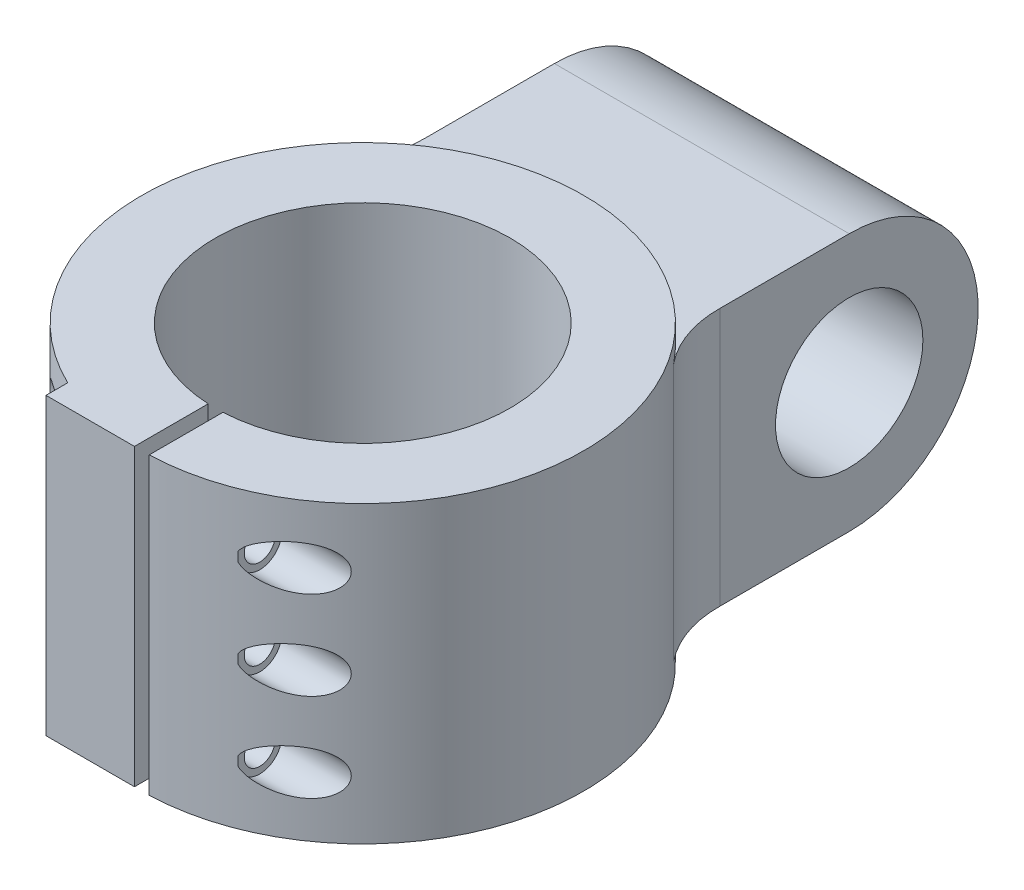
SolidWorks part; units mm, degrees
ref_plane "Płaszczyzna przednia" through (0, 0, 0) normal (0, 0, 1) x (1, 0, 0)
ref_plane "Płaszczyzna górna" through (0, 0, 0) normal (0, 1, 0) x (1, 0, 0)
ref_plane "Płaszczyzna prawa" through (0, 0, 0) normal (1, 0, 0) x (0, 0, -1)
sketch "Sketch1" plane through (0, 0, 0) normal (0, 1, 0) x (1, 0, 0)
  circle A0 centre (0, 0) radius 20
  circle A1 centre (0, 0) radius 30
  dimension "D1" = 40
  dimension "D2" = 60
extrude "Boss-Extrude1" add sketch "Sketch1" along normal blind 40
sketch "Sketch2" plane through (0, 40, 0) normal (0, 1, 0) x (1, 0, 0)
  line L0 (-1, 0) -> (1, 0)
  line L1 (1, 0) -> (1, -30)
  line L2 (1, -30) -> (-1, -30)
  line L3 (-1, -30) -> (-1, 0)
  circle A0 centre (0, 0) radius 30 construction
  point P4 (0, 0)
  dimension "D1" = 2
extrude "Cut-Extrude1" cut sketch "Sketch2" against normal through all
sketch "Sketch3" plane through (0, 40, 0) normal (0, 1, 0) x (1, 0, 0)
  line L0 (-1, -29.9833) -> (-13, -29.9833)
  line L1 (-13, -29.9833) -> (-13, -27.037)
  arc A0 (1, -29.9833) -> (-1, -29.9833) centre (0, 0) ccw construction
  arc A1 (-13, -27.037) -> (-1, -29.9833) centre (0, 0) ccw
  dimension "D1" = 12
extrude "Boss-Extrude2" add sketch "Sketch3" against normal up to surface (40 mm away) up to face at (0, 0, -0.0104)
hole_wizard "CBORE for M4 Hex Socket Head Cap Screw1" positions "Sketch4" profile "Sketch5" counterbore size "M4" standard "DIN"
sketch "Sketch4" plane through (-13, 0, 0) normal (-1, 0, 0) x (0, 0, 1)
  line L8 (29.9833, 40) -> (19.975, 40)
  line L9 (19.975, 40) -> (19.975, 0)
  line L10 (19.975, 0) -> (29.9833, 0)
  line L11 (29.9833, 0) -> (29.9833, 40)
  line L12 (29.9833, 40) -> (19.975, 40)
  line L13 (19.975, 40) -> (19.975, 0)
  line L14 (19.975, 0) -> (29.9833, 0)
  line L15 (29.9833, 0) -> (29.9833, 40)
  line L16 (19.975, 20) -> (24.9792, 20) construction
  line L18 (24.9792, 40) -> (24.9792, 20) construction
  point P0 (24.9792, 32)
  point P2 (24.9792, 20)
  point P4 (24.9792, 8)
  dimension "D2" = 12
  dimension "D3" = 12
  dimension "D1" = 0
sketch "Sketch5" plane through (-13, 32, 24.9792) normal (0, 1, 0) x (0, 0, 1)
  line L0 (0, 0) -> (0, 13.3519)
  line L1 (0, 13.3519) -> (2.25, 12)
  line L2 (2.25, 12) -> (2.25, 4)
  line L3 (2.25, 4) -> (3.75, 4)
  line L4 (3.75, 4) -> (3.75, 0)
  line L5 (3.75, 0) -> (0, 0)
  line L10 (0, 13.3519) -> (-2.25, 12) construction
  line L11 (0, -6.35) -> (0, 107.95) construction
  dimension "Hole Dia." = 4.5
  dimension "Hole Depth" = 12
  dimension "C'Bore Dia." = 7.5
  dimension "C'Bore Depth" = 4
  dimension "Drill Angle" = 118
sketch "Sketch6" plane through (-13, 0, 0) normal (-1, 0, 0) x (0, 0, 1)
  circle A0 centre (24.9792, 32) radius 3.75 construction
  circle A1 centre (24.9792, 20) radius 3.75 construction
  circle A2 centre (24.9792, 8) radius 3.75 construction
  circle A3 centre (24.9792, 32) radius 3.75
  circle A4 centre (24.9792, 20) radius 3.75
  circle A5 centre (24.9792, 8) radius 3.75
extrude "Cut-Extrude2" cut sketch "Sketch6" along normal through all
hole_wizard "Ø5.4 (5.4) Diameter Hole1" positions "Sketch7" profile "Sketch9" hole size "Ø5.4" standard "DIN" end condition through all
sketch "Sketch7" plane through (1, 0, 0) normal (-1, 0, 0) x (0, 0, 1)
  point P0 (24.9792, 8)
  point P3 (24.9792, 20)
  point P6 (24.9792, 32)
sketch "Sketch9" plane through (1, 8, 24.9792) normal (0, 1, 0) x (0, 0, 1)
  line L0 (0, 0) -> (0, 29)
  line L1 (0, 29) -> (2.1, 29)
  line L2 (2.1, 29) -> (2.1, 0)
  line L5 (2.1, 0) -> (0, 0)
  line L11 (0, -6.35) -> (0, 107.95) construction
  dimension "Thru Hole Dia." = 4.2
  dimension "Thru Hole Depth" = 29
ref_plane "Plane1" through (22, 0, 0) normal (-1, 0, 0) x (0, 0, 1)
sketch "Sketch10" plane through (22, 0, 0) normal (-1, 0, 0) x (0, 0, 1)
  circle A0 centre (24.9792, 8) radius 3
  circle A1 centre (24.9792, 32) radius 3
  circle A2 centre (24.9792, 20) radius 3
  dimension "D1" = 6
extrude "Cut-Extrude3" cut sketch "Sketch10" along normal blind 11
sketch "Sketch12" plane through (0, 40, 0) normal (0, 1, 0) x (1, 0, 0)
  line L0 (1, -29.9833) -> (1, 19.975)
  line L1 (-1, -29.9833) -> (-1, 19.975)
  line L4 (1, -19.975) -> (1, -29.9833)
  line L5 (-13, -27.037) -> (-13, -29.9833)
  line L6 (-13, -29.9833) -> (-1, -29.9833)
  line L7 (-1, -29.9833) -> (-1, -19.975)
  line L9 (-13, -27.037) -> (-13, -29.9833)
  line L10 (-13, -29.9833) -> (-1, -29.9833)
  arc A0 (1, -19.975) -> (-1, -19.975) centre (0, 0) ccw construction
  arc A2 (1, -29.9833) -> (-13, -27.037) centre (0, 0) ccw
  arc A3 (1, -19.975) -> (-1, -19.975) centre (0, 0) ccw
  arc A4 (1, -29.9833) -> (-13, -27.037) centre (0, 0) ccw
  arc A7 (1, 19.975) -> (-1, 19.975) centre (0, 0) ccw
  dimension "D1" = 0
extrude "Boss-Extrude3" [suppressed] add sketch "Sketch12" along normal blind 4
sketch "Sketch13" plane through (0, 0, 0) normal (1, 0, 0) x (0, 0, -1)
  line L0 (30, 40) -> (30, 0) construction
  line L1 (30, 20) -> (36, 20) construction
  line L2 (36, 20) -> (46, 20) construction
  line L3 (46, 37.5) -> (30, 37.5)
  line L4 (46, 2.5) -> (30, 2.5)
  line L5 (30, 2.5) -> (28.5, 2.5)
  line L6 (28.5, 2.5) -> (28.5, 37.5)
  line L7 (28.5, 37.5) -> (30, 37.5)
  circle A0 centre (46, 20) radius 10
  circle A1 centre (46, 20) radius 17.5
  dimension "D3" = 35
  dimension "D1" = 6
  dimension "D2" = 10
extrude "Boss-Extrude4" add sketch "Sketch13" along normal blind 20 and the other way blind 20 contours A1 L3 L7 L6 | A1 L6 L5 L4 | A1 A0 region at (0, 33.5911, -32.4089) region at (0, 32.0244, -58.0244) region at (0, 6.4089, -32.4089)
fillet "Fillet1" radius 15 2 edges at (-9.3675, 20, -28.5) (9.3675, 20, -28.5)
